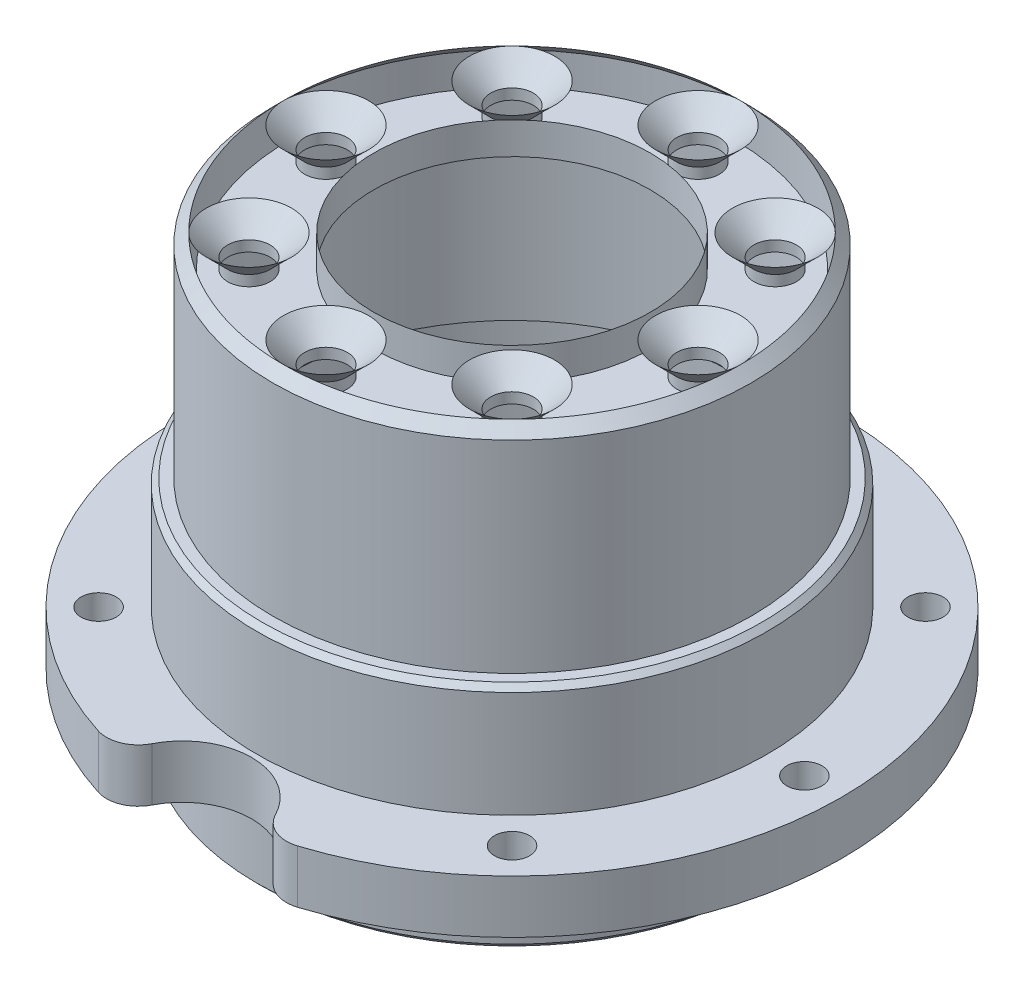
SolidWorks part; units mm, degrees
material "6061 合金"
ref_plane "前视基准面" through (0, 0, 0) normal (0, 0, 1) x (1, 0, 0)
ref_plane "上视基准面" through (0, 0, 0) normal (0, 1, 0) x (1, 0, 0)
ref_plane "右视基准面" through (0, 0, 0) normal (1, 0, 0) x (0, 0, -1)
sketch "草图1" plane through (0, 0, 0) normal (0, 0, 1) x (1, 0, 0)
  line L7 (-22.5, 35.5) -> (-13, 35.5)
  line L8 (-21, 32.5) -> (-13, 32.5)
  line L9 (-13, 35.5) -> (-13, 32.5)
  line L10 (-24, 15.5) -> (-22.5, 15.5)
  line L13 (-22.5, 35.5) -> (-22.5, 15.5)
  line L14 (-31, 0) -> (-24, 0)
  line L15 (-31, 5) -> (-31, 0)
  line L16 (-21, 32.5) -> (-21, 13.5)
  line L17 (-31, 5) -> (-24, 5)
  line L18 (-24, 15.5) -> (-24, 5)
  line L19 (0, 0) -> (0, 35.7412) construction
  line L22 (-22, -6) -> (-22, 13.5)
  line L23 (-22, 13.5) -> (-21, 13.5)
  line L24 (-24, 0) -> (-24, -6)
  line L25 (-24, -6) -> (-22, -6)
  dimension "D2" = 26
  dimension "D3" = 3
  dimension "D4" = 45
  dimension "D5" = 1.5
  dimension "D6" = 5
  dimension "D7" = 7
  dimension "D8" = 10.5
  dimension "D9" = 42
  dimension "D10" = 20
  dimension "D11" = 2
  dimension "D12" = 2
  dimension "D13" = 6
revolve "旋转1" add sketch "草图1" angle 360 about L19
hole_wizard "M4 螺纹孔1" positions "草图3" profile "草图4" tap size "M4" standard "GB" end condition through all
sketch "草图3" plane through (0, 5, 0) normal (0, 1, 0) x (1, 0, 0)
  circle A0 centre (0, 0) radius 27.5 construction
  circle A1 centre (0, 0) radius 31 construction
  point P0 (-19.4454, 19.4454)
  point P15 (0, 27.5)
  point P16 (19.4454, 19.4454)
  point P17 (27.5, 0)
  point P26 (19.4454, -19.4454)
  point P27 (0, -27.5)
  point P28 (-19.4454, -19.4454)
  point P29 (-27.5, 0)
  dimension "D1" = 8
  dimension "D2" = 3.5
sketch "草图4" plane through (-19.4454, 5, -19.4454) normal (1, 0, 0) x (0, 0, 1)
  line L0 (0, 0) -> (0, 11)
  line L1 (0, 11) -> (1.65, 11)
  line L2 (1.65, 11) -> (1.65, 0)
  line L5 (1.65, 0) -> (0, 0)
  line L11 (0, -6.35) -> (0, 107.95) construction
  dimension "通孔螺纹孔钻头直径" = 3.3
  dimension "通孔螺纹孔钻头深度" = 11
cosmetic thread "孔螺蚊线1" parameters "D2"=4
cosmetic thread "孔螺蚊线2" parameters "D2"=4
cosmetic thread "孔螺蚊线3" parameters "D2"=4
cosmetic thread "孔螺蚊线4" parameters "D2"=4
cosmetic thread "孔螺蚊线5" parameters "D2"=4
cosmetic thread "孔螺蚊线6" parameters "D2"=4
cosmetic thread "孔螺蚊线7" parameters "D2"=4
cosmetic thread "孔螺蚊线8" parameters "D2"=4
hole_wizard "孔1" positions "草图5" profile "草图6" legacy end condition through all
sketch "草图5" plane through (0, 35.5, 0) normal (0, 1, 0) x (1, 0, 0)
  circle A0 centre (0, 0) radius 17.5 construction
  point P0 (0, 17.5)
  point P29 (12.3744, 12.3744)
  point P30 (17.5, 0)
  point P31 (12.3744, -12.3744)
  point P32 (0, -17.5)
  point P33 (-12.3744, -12.3744)
  point P34 (-17.5, 0)
  point P38 (-12.3744, 12.3744)
  dimension "D1" = 35
  dimension "D2" = 8
sketch "草图6" plane through (0, 35.5, -17.5) normal (1, 0, 0) x (0, 0, 1)
  line L0 (0, 0) -> (0, 41.5)
  line L1 (0, 41.5) -> (2, 41.5)
  line L2 (2, 41.5) -> (2, 2)
  line L3 (2, 2) -> (4, 0)
  line L4 (4, 0) -> (0, 0)
  line L5 (0, -6.4453) -> (0, 115.525) construction
  line L6 (-2, 2) -> (-4, 0) construction
  dimension "直径" = 4
  dimension "深度" = 41.5
  dimension "锥坑角度" = 90
  dimension "锥坑直径" = 8
chamfer "倒角1" distance 0.5 angle 45 2 edges at (0, 15.5, -24) (0, -6, -24)
chamfer "倒角2" distance 1 angle 45 1 edges at (0, 35.5, -22.5)
sketch "草图7" plane through (0, 5, 0) normal (0, 1, 0) x (1, 0, 0)
  line L0 (0, 0) -> (0, -31) construction
  circle A0 centre (0, -32.5) radius 5 construction
  circle A3 centre (0, -31) radius 6.5
  circle A4 centre (0, 0) radius 31 construction
  dimension "D1" = 32.5
  dimension "D2" = 10
extrude "切除-拉伸1" cut sketch "草图7" against normal through all
fillet "圆角1" radius 3 2 edges at (6.4642, 2.5, 30.3185) (-6.4642, 2.5, 30.3185)
